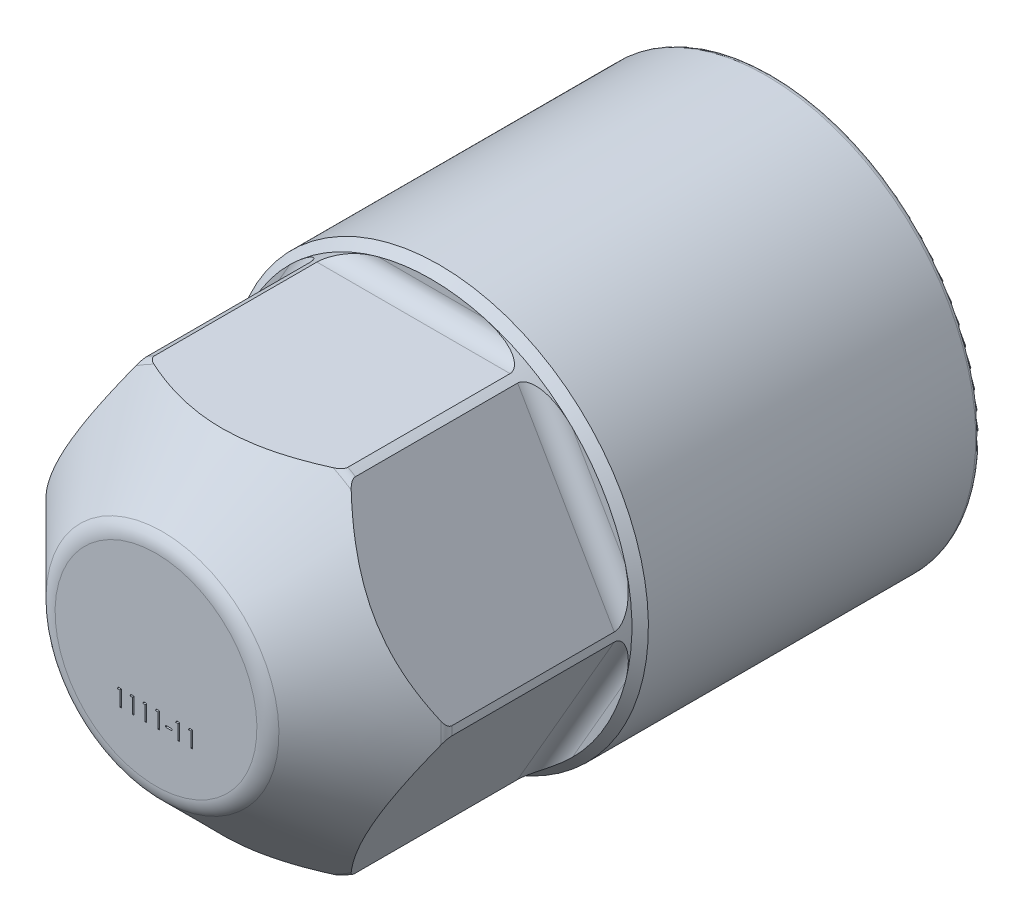
SolidWorks part; units mm, degrees
material "4340 H/T-Y"
ref_plane "Front Plane" through (0, 0, 0) normal (0, 0, 1) x (1, 0, 0)
ref_plane "Top Plane" through (0, 0, 0) normal (0, 1, 0) x (1, 0, 0)
ref_plane "Right Plane" through (0, 0, 0) normal (1, 0, 0) x (0, 0, -1)
sketch "Sketch1" plane through (0, 0, 0) normal (1, 0, 0) x (0, 0, -1)
  line L0 (0, 10.75) -> (0, 18.5)
  line L1 (-0.5, 19) -> (-30.25, 19)
  line L2 (-30.25, 19) -> (-31, 18.25)
  line L3 (-31, 18.25) -> (-47.3358, 18.25)
  line L4 (-48.0429, 17.9571) -> (-55.4142, 10.5858)
  line L5 (-56, 9.1716) -> (-56, 0)
  line L6 (-0.5, 10.25) -> (-5, 10.25)
  line L7 (-5, 10.25) -> (-6.25, 9)
  line L8 (-6.25, 9) -> (-48, 9)
  line L9 (-48, 9) -> (-51.2757, 0)
  line L10 (-51.2757, 0) -> (-56, 0)
  line L11 (0, 0) -> (-51.2757, 0) construction
  line L13 (-0.5, 10.25) -> (0, 10.75)
  arc A0 (-55.4142, 10.5858) -> (-56, 9.1716) centre (-54, 9.1716) ccw
  arc A1 (-48.0429, 17.9571) -> (-47.3358, 18.25) centre (-47.3358, 17.25) cw
  arc A2 (0, 18.5) -> (-0.5, 19) centre (-0.5, 18.5) ccw
  point P0 (0, 10.25)
  point P19 (-56, 10)
  point P22 (-47.75, 18.25)
  dimension "D14" = 2
  dimension "D19" = 1
  dimension "D15" = 0.5
  dimension "D1" = 38
  dimension "D2" = 20.5
  dimension "D3" = 36.5
  dimension "D4" = 45
  dimension "D5" = 25
  dimension "D6" = 45
  dimension "D7" = 20
  dimension "D8" = 56
  dimension "D9" = 70
  dimension "D10" = 48
  dimension "D11" = 18
  dimension "D12" = 45
  dimension "D13" = 5
  dimension "D16" = 31
revolve "Revolve1" add sketch "Sketch1" angle 360 about L11
cosmetic thread "Cosmetic Thread1" parameters "D1"=38, "D2"=20
ref_plane "Plane1" through (0, 0, 31) normal (0, 0, -1) x (-1, 0, 0)
sketch "Sketch2" plane through (0, 0, 31) normal (0, 0, 1) x (1, 0, 0)
  line L1 (-18.4752, 0) -> (-9.2376, -16)
  line L2 (-9.2376, -16) -> (9.2376, -16)
  line L3 (9.2376, -16) -> (18.4752, 0)
  line L4 (18.4752, 0) -> (9.2376, 16)
  line L5 (9.2376, 16) -> (-9.2376, 16)
  line L6 (-9.2376, 16) -> (-18.4752, 0)
  circle A0 centre (0, 0) radius 16 construction
  circle A1 centre (0, 0) radius 26.7692
  dimension "D2" = 53.5385
  dimension "D1" = 32
extrude "Cut-Extrude1" cut sketch "Sketch2" along normal blind 25
sketch "Sketch3" plane through (0, 0, 56) normal (0, 0, 1) x (1, 0, 0)
  line L0 (-7.6245, 2.4204) -> (7.6245, 2.4204) construction
  line L1 (-4.3471, -4.0007) -> (4.3471, -4.0007) construction
  text T0 " \r\n\r\n1111-11" font "Century Gothic" height 1.5
  point P5 (0, -4.0007)
  dimension "D1" = 4
extrude "Cut-Extrude2" cut sketch "Sketch3" against normal blind 0.25
sketch "Sketch4" plane through (13.8564, 8, 0) normal (0.866, 0.5, 0) x (0, 0, -1)
  line L0 (-51.2592, 0) -> (-33.0308, 0) construction
  text T0 "420Nm"
extrude "Cut-Extrude3" [suppressed] cut sketch "Sketch4" against normal blind 0.01
fillet "Fillet1" radius 1.6 6 edges at (-13.8564, 8, 31) (0, 16, 31) (13.8564, 8, 31) (13.8564, -8, 31) (0, -16, 31) (-13.8564, -8, 31)
